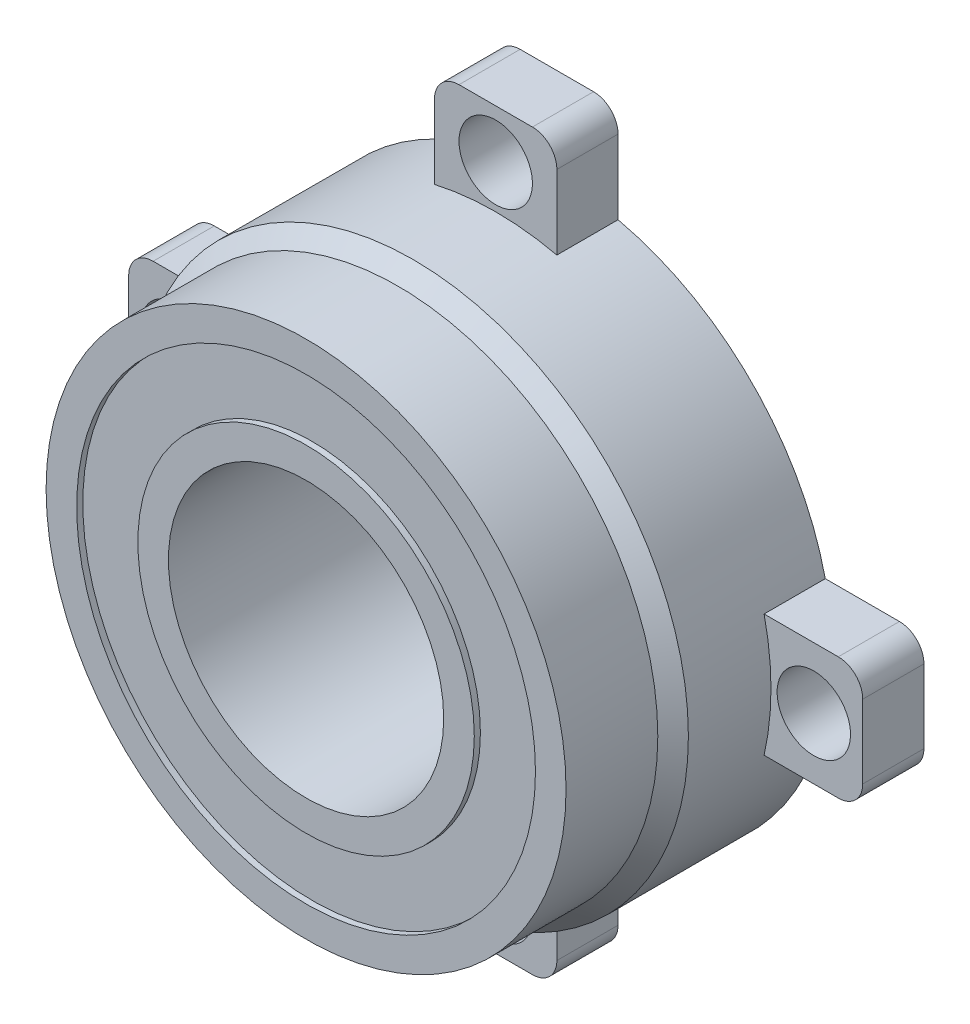
SolidWorks part; units mm, degrees
ref_plane "Płaszczyzna przednia" through (0, 0, 0) normal (0, 0, 1) x (1, 0, 0)
ref_plane "Płaszczyzna górna" through (0, 0, 0) normal (0, 1, 0) x (1, 0, 0)
ref_plane "Płaszczyzna prawa" through (0, 0, 0) normal (1, 0, 0) x (0, 0, -1)
sketch "Szkic1" plane through (0, 0, 0) normal (0, 0, 1) x (1, 0, 0)
  circle A0 centre (0, 0) radius 45
  circle A1 centre (0, 0) radius 22.5
  dimension "D1" = 90
  dimension "D2" = 45
extrude "Dodanie-wyciągnięcie1" add sketch "Szkic1" along normal blind 41
sketch "Szkic2" plane through (0, 0, 0) normal (0, 0, -1) x (-1, 0, 0)
  line L0 (35, 10) -> (56, 10)
  line L1 (-10, 35) -> (10, 35)
  line L2 (-10, 35) -> (-10, 56)
  line L3 (-6, 60) -> (6, 60)
  line L4 (10, 35) -> (10, 56)
  line L5 (-10, 35) -> (10, 60) construction
  line L6 (-10, 60) -> (10, 35) construction
  line L7 (35, 10) -> (35, -10)
  line L8 (35, -10) -> (56, -10)
  line L9 (60, 6) -> (60, -6)
  line L10 (10, -35) -> (10, -56)
  line L11 (10, -35) -> (-10, -35)
  line L12 (-10, -35) -> (-10, -56)
  line L13 (6, -60) -> (-6, -60)
  line L14 (-35, -10) -> (-56, -10)
  line L15 (-35, -10) -> (-35, 10)
  line L16 (-35, 10) -> (-56, 10)
  line L17 (-60, -6) -> (-60, 6)
  arc A1 (-10, 56) -> (-6, 60) centre (-6, 56) cw
  arc A2 (6, 60) -> (10, 56) centre (6, 56) cw
  arc A3 (56, 10) -> (60, 6) centre (56, 6) cw
  arc A4 (60, -6) -> (56, -10) centre (56, -6) cw
  arc A5 (10, -56) -> (6, -60) centre (6, -56) cw
  arc A6 (-6, -60) -> (-10, -56) centre (-6, -56) cw
  arc A7 (-56, -10) -> (-60, -6) centre (-56, -6) cw
  arc A8 (-60, 6) -> (-56, 10) centre (-56, 6) cw
  point P0 (0, 45)
  point P13 (0, 0)
  point P40 (0, 0)
  dimension "D1" = 4
  dimension "D3" = 20
  dimension "D4" = 25
  dimension "D5" = 35
  dimension "D6" = 10
  dimension "D7" = 35
  dimension "D8" = 10
  dimension "D9" = 35
  dimension "D10" = 10
  dimension "D11" = 10
  dimension "D2" = 4
extrude "Dodanie-wyciągnięcie2" add sketch "Szkic2" against normal blind 10
sketch "Szkic3" plane through (0, 0, 0) normal (0, 0, -1) x (-1, 0, 0)
  line L0 (10, 43.8748) -> (10, 56) construction
  circle A0 centre (0, 52) radius 6
  point P2 (0, 0)
  dimension "D1" = 12
  dimension "D2" = 52
  dimension "D3" = 10
extrude "Wytnij-wyciągnięcie1" cut sketch "Szkic3" against normal blind 10
pattern_circular "Szyk kołowy1" count 4 every 90 about axis through (0, 0, 0) along (0, 0, 1) of "Wytnij-wyciągnięcie1"
sketch "Szkic5" plane through (0, 0, 41) normal (0, 0, 1) x (1, 0, 0)
  circle A0 centre (0, 0) radius 42.5
  circle A1 centre (0, 0) radius 45
  dimension "D1" = 85
extrude "Wytnij-wyciągnięcie2" cut sketch "Szkic5" against normal blind 20
sketch "Szkic6" plane through (0, 0, 41) normal (0, 0, 1) x (1, 0, 0)
  circle A0 centre (0, 0) radius 27.5
  circle A1 centre (0, 0) radius 37.5
  dimension "D1" = 55
  dimension "D2" = 75
extrude "Wytnij-wyciągnięcie3" cut sketch "Szkic6" against normal blind 1
chamfer "Sfazowanie1" distance 5 angle 45 1 edges at (42.5, 0, 21)
